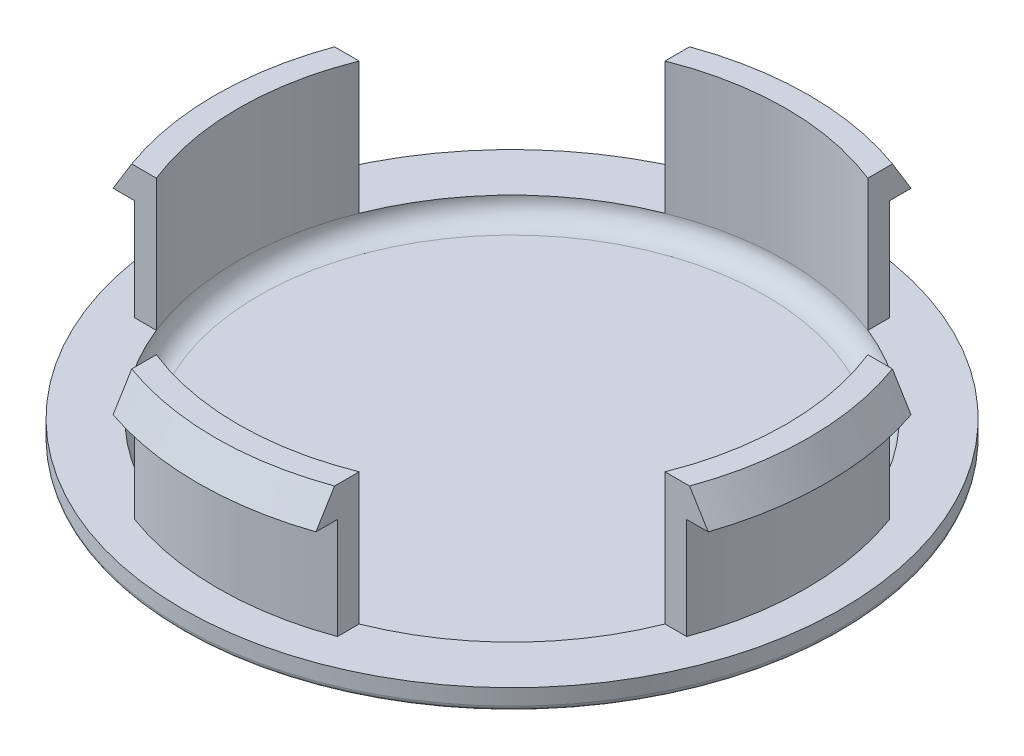
SolidWorks part; units mm, degrees
ref_plane "Спереди" through (0, 0, 0) normal (0, 0, 1) x (1, 0, 0)
ref_plane "Сверху" through (0, 0, 0) normal (0, 1, 0) x (1, 0, 0)
ref_plane "Справа" through (0, 0, 0) normal (1, 0, 0) x (0, 0, -1)
sketch "Эскиз1" plane through (0, 0, 0) normal (0, 0, 1) x (1, 0, 0)
  line L0 (0, 0) -> (0, -17.5509) construction
  line L1 (0, 0) -> (-40.7219, 0) construction
  line L2 (-32.5, 2.9251) -> (-32.5, 4.5)
  line L3 (-32.5, 4.5) -> (-29, 4.5)
  line L4 (-29, 4.5) -> (-29, 14.5)
  line L5 (-29, 14.5) -> (-31, 14.5)
  line L6 (-31, 14.5) -> (-29.2679, 17.5)
  line L7 (-29.2679, 17.5) -> (-27, 17.5)
  line L8 (-27, 17.5) -> (-27, 4.5)
  line L9 (-25, 2.5) -> (0, 2.5)
  line L10 (0, 2.5) -> (0, 0)
  arc A0 (0, 0) -> (-32.0799, 2.4315) centre (-1.7314, 189.9921) cw
  arc A1 (-32.5, 2.9251) -> (-32.0799, 2.4315) centre (-32, 2.9251) ccw
  arc A2 (-27, 4.5) -> (-25, 2.5) centre (-25, 4.5) ccw
  point P5 (-32.5, 4.5)
  point P18 (-32.3876, 4.5)
  point P20 (-32.5, 2.5)
  dimension "D10" = 2
  dimension "D11" = 0.5
  dimension "D12" = 190
  dimension "D13" = 2
  dimension "D1" = 65
  dimension "D2" = 58
  dimension "D3" = 62
  dimension "D4" = 4.5
  dimension "D5" = 2.5
  dimension "D6" = 4
  dimension "D7" = 3
  dimension "D8" = 10
  dimension "D9" = 60
  dimension "D14" = 2
revolve "Повернуть1" add sketch "Эскиз1" angle 360 about L0
sketch "Эскиз2" plane through (0, 17.5, 0) normal (0, 1, 0) x (1, 0, 0)
  line L0 (0, 0) -> (0, 37.57) construction
  line L1 (-10, 40.8566) -> (-10, 14.3515)
  line L2 (10, 40.8566) -> (10, 14.3515)
  line L3 (40.8566, 10) -> (14.3515, 10)
  line L4 (40.8566, -10) -> (14.3515, -10)
  line L5 (10, -40.8566) -> (10, -14.3515)
  line L6 (-10, -40.8566) -> (-10, -14.3515)
  line L7 (-40.8566, -10) -> (-14.3515, -10)
  line L8 (-40.8566, 10) -> (-14.3515, 10)
  circle A0 centre (0, 0) radius 17.4918
  circle A1 centre (0, 0) radius 42.0626
  point P24 (0, 0)
  circle M1 centre (0, 0) radius 29.2679
  circle M2 centre (0, 0) radius 27
  dimension "D1" = 20
  dimension "D2" = 4
extrude "Вырез-Вытянуть1" cut sketch "Эскиз2" against normal up to surface (13 mm away) contours L1 A1 L8 M1 | L3 L2 M1 M2 | L3 A1 L2 M1 | L5 A1 L4 M1 | L5 L4 M1 M2 | L7 A1 L6 M1 | L7 L6 M1 M2 | L8 L1 M1 M2 region at (-24.5638, 17.5, -24.5638) region at (-19.3271, 17.5, -19.3271) region at (24.5638, 17.5, -24.5638) region at (19.3271, 17.5, -19.3271) region at (-24.5638, 17.5, 24.5638) region at (-19.3271, 17.5, 19.3271) region at (24.5638, 17.5, 24.5638) region at (19.3271, 17.5, 19.3271) up to face at (0, 4.5, 32.5)
sketch "Эскиз3" plane through (0, 0, 0) normal (0, 1, 0) x (1, 0, 0)
  line L0 (-0.1, 0) -> (-13.6, 0) construction
  line L1 (-13.6, 0) -> (-13.6, 7.8173) construction
  line L2 (-13.6, 7.8173) -> (-27.1, 0)
  line L3 (-13.6, -7.8173) -> (-27.1, 0)
  line L4 (-13.6, -7.8173) -> (-0.1, 0)
  line L5 (-13.6, 7.8173) -> (-0.1, 0)
  line L14 (0, 0) -> (-0.1, 0) construction
  line L15 (13.57, 7.8693) -> (13.55, 23.4693)
  line L16 (0.03, 15.6866) -> (13.55, 23.4693)
  line L17 (0.03, 15.6866) -> (0.05, 0.0866)
  line L18 (13.57, 7.8693) -> (0.05, 0.0866)
  line L19 (0.05, 0.0866) -> (6.8, 11.7779) construction
  line L20 (6.8, 11.7779) -> (13.57, 7.8693) construction
  line L21 (0, 0) -> (0.05, 0.0866) construction
  line L22 (0.03, -15.6866) -> (13.55, -23.4693)
  line L23 (13.57, -7.8693) -> (13.55, -23.4693)
  line L24 (13.57, -7.8693) -> (0.05, -0.0866)
  line L25 (0.03, -15.6866) -> (0.05, -0.0866)
  line L26 (0.05, -0.0866) -> (6.8, -11.7779) construction
  line L27 (6.8, -11.7779) -> (0.03, -15.6866) construction
  line L28 (0, 0) -> (0.05, -0.0866) construction
  line L29 (0, 0) -> (-0.1, 0) construction
  dimension "D1" = 15.6
  dimension "D2" = 13.5
  dimension "D4" = 3
  dimension "D5" = 0.1
extrude "Бобышка-Вытянуть4" add sketch "Эскиз3" along normal up to surface (2.5 mm away) and the other way blind 5 up to face at (0, 2.5, 25)
sketch "Эскиз4" plane through (0, 0, 0) normal (0, 0, 1) x (1, 0, 0)
  line L0 (0, 0) -> (0, -2.5) construction
  line L1 (0, -18.2196) -> (-32.5, -18.2196)
  line L2 (-32.5, -18.2196) -> (-32.5, 2)
  line L3 (0, -2.5) -> (0, -18.2196)
  arc A2 (0, -2.5) -> (-32.5, 2) centre (-0.7537, 111.6676) cw
  point P7 (-32.5, -5.9497)
  point P8 (0, -15.0207)
  point P9 (-32.5, -14.4835)
  point P10 (0, -2.1953)
  point P11 (-32.5, -4.0161)
  point P12 (0, -18.2346)
  point P13 (0, -3.5104)
  point P14 (-32.5, -15.2196)
  point P15 (-32.5, 1.3915)
  point P16 (-32.5, 2.5)
  dimension "D1" = 65
  dimension "D2" = 114.1701
  dimension "D3" = 2.5
  dimension "D4" = 4.5
revolve "Вырез-Повернуть2" cut sketch "Эскиз4" angle 360 about L0
